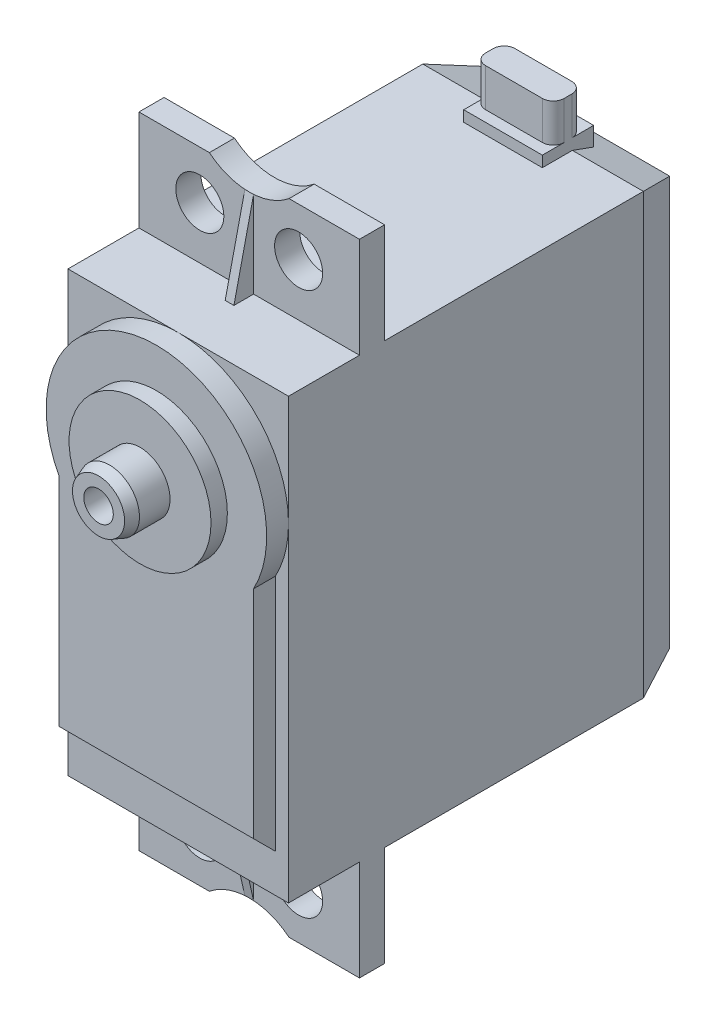
SolidWorks part; units mm, degrees
ref_plane "Front Plane" through (0, 0, 0) normal (0, 0, 1) x (1, 0, 0)
ref_plane "Top Plane" through (0, 0, 0) normal (0, 1, 0) x (1, 0, 0)
ref_plane "Right Plane" through (0, 0, 0) normal (1, 0, 0) x (0, 0, -1)
sketch "Sketch1" plane through (0, 0, 0) normal (1, 0, 0) x (0, 0, -1)
  line L0 (0, 35.7892) -> (0, -31.2562) construction
  line L1 (-8.8, -20.1) -> (-8.8, 20.1)
  line L2 (-8.8, 20.1) -> (-2.3, 20.1)
  line L3 (-2.3, 20.1) -> (-2.3, 29.3)
  line L4 (-2.3, 29.3) -> (0, 29.3)
  line L5 (0, 29.3) -> (0, 20.1)
  line L6 (0, 20.1) -> (27.5, 20.1)
  line L7 (27.5, 20.1) -> (27.5, -20.1)
  line L8 (27.5, 0) -> (-8.8, 0) construction
  line L9 (-2.3, -29.3) -> (0, -29.3)
  line L10 (0, -35.7892) -> (0, 31.2562) construction
  line L11 (0, -20.1) -> (27.5, -20.1)
  line L12 (0, -29.3) -> (0, -20.1)
  line L13 (-2.3, -20.1) -> (-2.3, -29.3)
  line L14 (-8.8, -20.1) -> (-2.3, -20.1)
  dimension "D1" = 27.5
  dimension "D2" = 9.2
  dimension "D3" = 2.3
  dimension "D4" = 6.5
  dimension "D5" = 40.2
extrude "Boss-Extrude1" add sketch "Sketch1" along normal blind 10.1 and the other way blind 10.1
sketch "Sketch2" plane through (0, 0, 2.3) normal (0, 0, 1) x (1, 0, 0)
  line L0 (-13.4129, 0) -> (14.9559, 0) construction
  line L1 (0, 30.5647) -> (0, -8.4869) construction
  line L3 (-10.1, 29.3) -> (10.1, 29.3) construction
  line L4 (-2.855, 28) -> (2.9288, 28) construction
  line L5 (-3.65, 29.3) -> (3.65, 29.3)
  line L6 (-3.65, -29.3) -> (3.65, -29.3)
  circle A0 centre (4.525, 24.9) radius 2.2
  circle A1 centre (-4.525, 24.9) radius 2.2
  arc A2 (3.65, 29.3) -> (-3.65, 29.3) centre (0, 33.774) cw
  arc A3 (3.65, -29.3) -> (-3.65, -29.3) centre (0, -33.774) ccw
  circle A4 centre (-4.525, -24.9) radius 2.2
  circle A5 centre (4.525, -24.9) radius 2.2
  point P16 (0, 28)
  dimension "D1" = 4.4
  dimension "D3" = 4.4
  dimension "D4" = 1.3
  dimension "D2" = 9.05
  dimension "D5" = 7.3
extrude "Cut-Extrude1" cut sketch "Sketch2" against normal up to next
sketch "Sketch3" plane through (0, 0, 0) normal (1, 0, 0) x (0, 0, -1)
  line L0 (-2.3, 28) -> (-4.1, 20.1)
  line L1 (-8.8, 20.1) -> (-2.3, 20.1) construction
  line L2 (-2.3, 20.1) -> (-2.3, 29.3) construction
  line L3 (-13.8798, 0) -> (32.4294, 0) construction
  dimension "D1" = 1.8
rib "Rib3" sketch "Sketch3" sketch "Sketch3" thickness 0.8 extrusion direction parallel to sketch draft on no parameters "D1"=0.8
mirror "Mirror1" about plane through (0, 0, 0) normal (0, 1, 0) of "Rib3"
sketch "Sketch4" plane through (0, 0, 8.8) normal (0, 0, 1) x (1, 0, 0)
  line L0 (0, 4.8073) -> (0, -13.947) construction
  line L1 (8.9, 5.2251) -> (8.9, -16.6)
  line L2 (8.9, -16.6) -> (-8.9, -16.6)
  line L3 (10.1, 20.1) -> (10.1, -20.1) construction
  line L5 (-10.1, -20.1) -> (10.1, -20.1) construction
  line L6 (-10.1, 20.1) -> (-10.1, -20.1) construction
  line L7 (-10.1, 20.1) -> (10.1, 20.1) construction
  line L8 (-8.9, 5.2251) -> (-8.9, -16.6)
  arc A0 (8.9, 5.2251) -> (-8.9, 5.2251) centre (0, 10) ccw
  point P17 (0, -16.6)
  dimension "D1" = 1.2
  dimension "D2" = 3.5
extrude "Boss-Extrude2" add sketch "Sketch4" along normal blind 2
chamfer "Chamfer1" distance 2 angle 45 1 edges at (0, -16.6, 10.8)
sketch "Sketch5" plane through (0, 0, 10.8) normal (0, 0, 1) x (1, 0, 0)
  circle A0 centre (0, 10) radius 6.5
  dimension "D1" = 13
extrude "Boss-Extrude3" add sketch "Sketch5" along normal blind 1.5
chamfer "Chamfer2" distance 3.8 angle 20 4 edges at (-10.1, 0, -27.5) (0, -20.1, -27.5) (10.1, 0, -27.5) (0, 20.1, -27.5) first distance on face at (-10.1, 0.7692, -1.4923) first distance on face at (0, -20.1, -13.75) first distance on face at (10.1, 0.7692, -1.4923) first distance on face at (0, 20.1, -13.75)
sketch "Sketch6" plane through (0, 0, 0) normal (1, 0, 0) x (0, 0, -1)
  line L0 (25.65, 18.7169) -> (20.95, 18.7169)
  line L1 (20.95, 18.7169) -> (20.95, 21.1)
  line L2 (20.95, 21.1) -> (21.95, 21.1)
  line L3 (21.95, 21.1) -> (21.95, 24.6)
  line L4 (21.95, 24.6) -> (24.65, 24.6)
  line L5 (24.65, 24.6) -> (24.65, 21.1106)
  line L6 (24.65, 21.1106) -> (25.65, 21.1106)
  line L7 (25.65, 21.1106) -> (25.65, 18.7169)
  line L8 (23.3, 25.7633) -> (23.3, 17.4607) construction
  line L9 (27.5, 18.7169) -> (27.5, -18.7169) construction
  line L10 (23.7, 20.1) -> (0, 20.1) construction
  point P12 (23.3, 24.6)
  point P13 (23.3, 18.7169)
  dimension "D1" = 4.2
  dimension "D2" = 2.7
  dimension "D3" = 4.7
  dimension "D4" = 1
  dimension "D5" = 3.5
extrude "Boss-Extrude4" add sketch "Sketch6" along normal blind 3.6 and the other way blind 3.6
fillet "Fillet2" radius 1 4 edges at (-3.6, 22.85, -21.95) (-3.6, 22.8553, -24.65) (3.6, 22.85, -21.95) (3.6, 22.8553, -24.65)
sketch "Sketch7" plane through (0, 0, 12.3) normal (0, 0, 1) x (1, 0, 0)
  circle A0 centre (0, 10) radius 2.75
  circle A1 centre (0, 10) radius 1.35
  dimension "D1" = 5.5
  dimension "D2" = 2.7
extrude "Boss-Extrude5" add sketch "Sketch7" along normal blind 3.8
chamfer "Chamfer3" distance 1 angle 20 1 edges at (2.75, 10, 16.1) first distance on face at (2.75, 10, 16.1)
